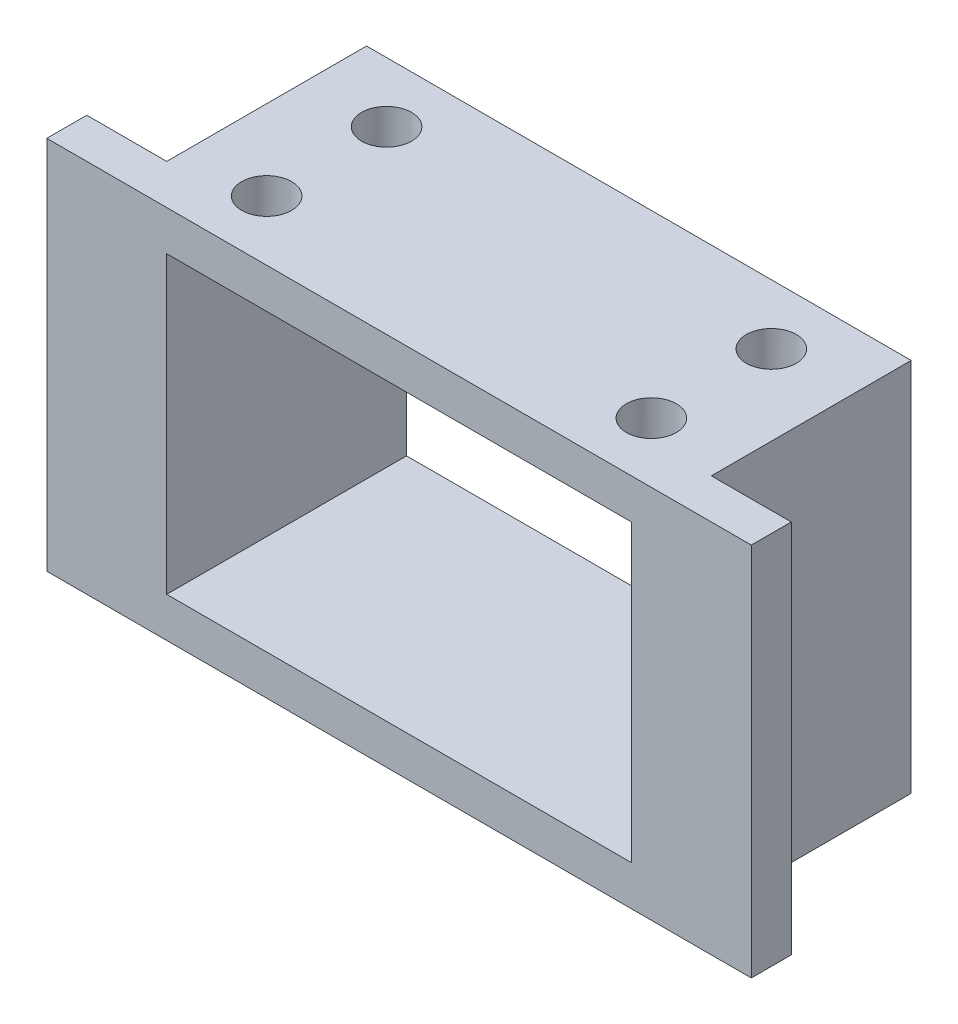
SolidWorks part; units mm, degrees
ref_plane "Front Plane" through (0, 0, 0) normal (0, 0, 1) x (1, 0, 0)
ref_plane "Top Plane" through (0, 0, 0) normal (0, 1, 0) x (1, 0, 0)
ref_plane "Right Plane" through (0, 0, 0) normal (1, 0, 0) x (0, 0, -1)
sketch "Sketch1" plane through (0, 0, 0) normal (0, 0, 1) x (1, 0, 0)
  line L0 (-2, 2) -> (25.25, 2)
  line L1 (0, 0) -> (23.25, 0)
  line L2 (0, 0) -> (0, -14.76)
  line L3 (0, -14.76) -> (23.25, -14.76)
  line L4 (23.25, 0) -> (23.25, -14.76)
  line L5 (25.25, 2) -> (25.25, -16.76)
  line L6 (-2, -16.76) -> (25.25, -16.76)
  line L7 (-2, 2) -> (-2, -16.76)
  dimension "D1" = 14.76
  dimension "D2" = 23.25
  dimension "D3" = 2
extrude "Boss-Extrude1" add sketch "Sketch1" along normal blind 18
sketch "Sketch3" plane through (0, 0, 0) normal (0, 0, -1) x (-1, 0, 0)
  line L1 (-23.25, 0) -> (0, 0)
  line L2 (-23.25, 0) -> (-23.25, -14.76)
  line L3 (-23.25, -14.76) -> (0, -14.76)
  line L4 (0, 0) -> (0, -14.76)
extrude "Boss-Extrude2" add sketch "Sketch3" against normal blind 2
sketch "Sketch7" plane through (-2, 0, 0) normal (-1, 0, 0) x (0, 0, 1)
  line L0 (18, 2) -> (0, 2) construction
  line L1 (2, -4) -> (4, -4)
  line L2 (2, -4) -> (2, -9)
  line L3 (2, -9) -> (4, -9)
  line L4 (4, -4) -> (4, -9)
  line L6 (0, 2) -> (0, -16.76) construction
  dimension "D1" = 6
  dimension "D2" = 5
  dimension "D3" = 2
  dimension "D4" = 2
extrude "Cut-Extrude1" cut sketch "Sketch7" against normal blind 2
sketch "Sketch10" plane through (0, 0, 18) normal (0, 0, 1) x (1, 0, 0)
  line L1 (-2, 2) -> (25.25, 2)
  line L2 (-2, 2) -> (-2, -16.76)
  line L3 (-2, -16.76) -> (25.25, -16.76)
  line L4 (25.25, 2) -> (25.25, -16.76)
  line L5 (0, 0) -> (23.25, 0)
  line L6 (0, 0) -> (0, -14.76)
  line L7 (0, -14.76) -> (23.25, -14.76)
  line L8 (23.25, 0) -> (23.25, -14.76)
  line L10 (-2, -0.0396) -> (-2, -13.0396)
  line L13 (-2, 2) -> (-9, 2)
  line L14 (-2, 2) -> (-2, -16.76)
  line L15 (-2, -16.76) -> (-9, -16.76)
  line L16 (-9, 2) -> (-9, -16.76)
  line L17 (25.25, 2) -> (32.25, 2)
  line L18 (25.25, 2) -> (25.25, -16.76)
  line L19 (25.25, -16.76) -> (32.25, -16.76)
  line L20 (32.25, 2) -> (32.25, -16.76)
  line M7 (-2, 2) -> (-2, -16.76)
  line M8 (-2, -16.76) -> (25.25, -16.76)
  line M9 (25.25, -16.76) -> (25.25, 2)
  line M10 (25.25, 2) -> (-2, 2)
  line M11 (23.25, -14.76) -> (0, -14.76)
  line M12 (0, -14.76) -> (0, 0)
  line M13 (0, 0) -> (23.25, 0)
  line M14 (23.25, 0) -> (23.25, -14.76)
  dimension "D1" = 7
  dimension "D2" = 7
extrude "Boss-Extrude3" add sketch "Sketch10" along normal blind 2 contours L13 L16 L15 L2 M7 | L2 M10 M7 M8 M9 M14 M11 M12 M13 | L20 L17 L19 M9 region at (11.625, 1.6692, 18) region at (-5.5, -7.38, 18) region at (28.75, -7.38, 18)
sketch "Sketch11" plane through (0, 0, 18) normal (0, 0, -1) x (-1, 0, 0)
  line L0 (2, 2) -> (9, 2) construction
  line L1 (6, 2) -> (3, 2)
  line L3 (6, -16.76) -> (3, -16.76)
  line L5 (2, -16.76) -> (9, -16.76) construction
  line L7 (2, 2) -> (2, -16.76) construction
  circle A0 centre (3.5, -8.26) radius 1.5
  dimension "D1" = 8.5
  dimension "D2" = 1.5
extrude "Cut-Extrude3" cut sketch "Sketch11" against normal blind 2 contours A0 | A0 | A0 | A0 region at (-3.5, -8.26, 18)
sketch "Sketch12" plane through (0, 0, 18) normal (0, 0, -1) x (-1, 0, 0)
  line L0 (-32.25, 2) -> (-25.25, 2) construction
  line L1 (-31, 2) -> (-28, 2)
  line L3 (-31, -16.76) -> (-28, -16.76)
  line L5 (-32.25, -16.76) -> (-25.25, -16.76) construction
  line L7 (-25.25, -16.76) -> (-25.25, 2) construction
  circle A0 centre (-26.95, -8.26) radius 1.5
  dimension "D1" = 8.5
  dimension "D2" = 1.7
extrude "Cut-Extrude4" cut sketch "Sketch12" against normal blind 2 contours A0 | A0 | A0 | A0 region at (26.95, -8.26, 18)
fillet "Fillet11" radius 1 6 edges at (0, -9, 3) (0, -4, 3) (0, -6.5, 4) (-2, -6.5, 4) (-2, -4, 3) (-2, -9, 3)
sketch "Sketch13" plane through (0, 0, 18) normal (0, 0, -1) x (-1, 0, 0)
  line L0 (-32.25, -16.76) -> (-25.25, -16.76) construction
  line L1 (-32.25, 2) -> (-29.25, 2)
  line L2 (-32.25, 2) -> (-32.25, -16.76)
  line L3 (-32.25, -16.76) -> (-29.25, -16.76)
  line L4 (-29.25, 2) -> (-29.25, -16.76)
  line L5 (2, -16.76) -> (9, -16.76) construction
  line L6 (9, 2) -> (6, 2)
  line L7 (9, 2) -> (9, -16.76)
  line L8 (9, -16.76) -> (6, -16.76)
  line L9 (6, 2) -> (6, -16.76)
  dimension "D1" = 3
  dimension "D2" = 3
extrude "Cut-Extrude5" cut sketch "Sketch13" against normal blind 10
sketch "Sketch14" plane through (0, 2, 0) normal (0, 1, 0) x (1, 0, 0)
  line L0 (25.25, -18) -> (25.25, 0) construction
  line L1 (-2, 0) -> (25.25, 0)
  line L2 (-2, 0) -> (-2, -8)
  line L3 (-2, -8) -> (25.25, -8)
  line L4 (25.25, 0) -> (25.25, -8)
  line L5 (-2, -18) -> (-6, -18) construction
  dimension "D1" = 10
extrude "Cut-Extrude6" cut sketch "Sketch14" against normal up to surface (18.76 mm away) up to face at (11.625, -16.76, 14)
sketch "Sketch16" plane through (0, 0, 20) normal (0, 0, 1) x (1, 0, 0)
  line L5 (0, -14.76) -> (0, -16.76)
  line L6 (29.25, -16.76) -> (-6, -16.76) construction
  line L7 (0, -16.76) -> (23.25, -16.76)
  line L8 (23.25, -16.76) -> (23.25, -14.76)
  line L10 (0, -14.76) -> (23.25, -14.76)
  line L14 (23.25, -14.76) -> (23.25, 0)
  line L15 (0, -14.76) -> (23.25, -14.76)
  line L16 (0, 0) -> (0, -14.76)
  line L17 (23.25, 0) -> (0, 0)
  line L18 (23.25, -14.76) -> (23.25, 0)
  line L20 (0, 0) -> (0, -14.76)
  line L21 (23.25, 0) -> (0, 0)
  line M4 (-6, -16.76) -> (29.25, -16.76)
  line M8 (23.25, -14.76) -> (0, -14.76)
  dimension "D1" = 0
extrude "Boss-Extrude5" add sketch "Sketch16" along normal blind 7.6 contours L8 L5 M4 M8 region at (11.625, -15.76, 20)
sketch "Sketch19" plane through (0, 0, 8) normal (0, 0, -1) x (-1, 0, 0)
  line L0 (-26.95, -6.76) -> (-23.25, -6.76)
  line L1 (-23.25, -14.76) -> (-23.25, 0) construction
  line L2 (-23.25, -6.76) -> (-23.25, -7.75)
  line L3 (-23.25, -7.75) -> (-25.25, -7.75)
  line L4 (-25.25, -16.76) -> (-25.25, 2) construction
  line L5 (-25.25, -7.75) -> (-25.25, -6.76)
  line L6 (-25.25, -16.76) -> (-25.25, 2) construction
  line L7 (3.5, -6.76) -> (0, -6.76)
  line L8 (0, 0) -> (0, -14.76) construction
  line L9 (0, -6.76) -> (0, -7.75)
  line L10 (0, -7.75) -> (2, -7.75)
  line L11 (2, -8.26) -> (2, -16.76) construction
  line L12 (2, -7.75) -> (2, -6.76)
  line L13 (2, 2) -> (2, -8.26) construction
  line L14 (-25.25, -6.76) -> (-23.25, -6.76)
  line L15 (-23.25, -7.75) -> (-25.25, -7.75)
  line L16 (0, -6.76) -> (2, -6.76)
  line L17 (2, -7.75) -> (0, -7.75)
  circle A0 centre (-26.95, -8.26) radius 1.5 construction
  circle A1 centre (3.5, -8.26) radius 1.5 construction
  line M1 (0, 0) -> (0, -14.76)
  line M3 (-23.25, -14.76) -> (-23.25, 0)
  line M6 (2, -16.76) -> (2, 2)
  line M8 (-25.25, 2) -> (-25.25, -16.76)
extrude "Cut-Extrude8" cut sketch "Sketch19" against normal up to surface (10 mm away) contours L10 L7 M1 M6 | L3 L0 M3 M8 region at (24.25, -7.255, 8) region at (-1, -7.255, 8) up to face at (25.45, -8.26, 18)
sketch "Sketch20" plane through (0, -16.76, 0) normal (0, -1, 0) x (1, 0, 0)
  line L0 (2, 17) -> (18.6, 17)
  line L1 (25.25, 8) -> (-2, 8) construction
  line L2 (-2, 18) -> (-2, 8) construction
  line L3 (1.3222, 20.5938) -> (20.8547, 23.0246)
  line L4 (1.5074, 19.1053) -> (21.0399, 21.536)
  line L5 (1.0027, 14.9575) -> (19.59, 12.6444)
  line L6 (0.8174, 13.469) -> (19.4048, 11.1559)
  circle A0 centre (18.6, 17) radius 4.2
  circle A1 centre (2, 17) radius 2.15
  circle A2 centre (2, 17) radius 3.65
  circle A3 centre (18.6, 17) radius 5.7
  line M9 (29.25, 20) -> (23.25, 20)
  line M10 (23.25, 20) -> (23.25, 27.6)
  line M12 (0, 27.6) -> (0, 20)
  line M13 (0, 20) -> (-6, 20)
  dimension "D1" = 8.4
  dimension "D2" = 4.3
  dimension "D3" = 16.6
  dimension "D4" = 9
  dimension "D5" = 4
  dimension "D6" = 1.5
  dimension "D7" = 1.5
extrude "Boss-Extrude6" add sketch "Sketch20" along normal blind 4 contours L4 A2 L5 A1 M12 M13 | A3 L3 A2 L4 | A3 L4 A0 L5 M10 M9 | A3 L5 A2 L6 region at (-0.2465, -16.76, 17) region at (9.5346, -16.76, 20.9168) region at (9.5346, -16.76, 13.0832) region at (15.9644, -16.76, 21.8821)
sketch "Sketch21" plane through (0, -16.76, 0) normal (0, -1, 0) x (1, 0, 0)
  circle A0 centre (18.6, 17) radius 1.25
  dimension "D1" = 2.5
extrude "Cut-Extrude9" cut sketch "Sketch21" against normal up to surface (2 mm away) up to face at (11.625, -14.76, 18.5333)
sketch "Sketch23" plane through (0, -16.76, 0) normal (0, -1, 0) x (1, 0, 0)
  line L0 (11.1, 21.1007) -> (0.4062, 19.9989)
  line L1 (0.4062, 19.9989) -> (-0.9545, 17.32)
  line L2 (-0.9545, 17.32) -> (0.3877, 14.426)
  line L3 (0.3877, 14.426) -> (11.1, 12.8678)
  line L4 (11.1, 12.8678) -> (11.1, 21.1007)
  circle A0 centre (18.6, 17) radius 1.25 construction
  dimension "D1" = 7.5
extrude "Boss-Extrude7" add sketch "Sketch23" along normal blind 1
sketch "Sketch24" plane through (0, -16.76, 0) normal (0, -1, 0) x (1, 0, 0)
  line L0 (0.8326, 20.5329) -> (21.7275, 23.1332)
  line L1 (0, 20) -> (0, 27.6)
  line L2 (0, 27.6) -> (23.25, 27.6)
  line L3 (23.25, 27.6) -> (23.25, 20)
  circle A0 centre (2, 17) radius 3.65
  circle A1 centre (18.6, 17) radius 5.7
  arc M2 (17.8961, 22.6564) -> (23.25, 20.2966) centre (18.6, 17) cw
  line M3 (23.25, 20.2966) -> (23.25, 27.6)
  line M4 (23.25, 27.6) -> (0, 27.6)
  line M5 (0, 27.6) -> (0, 20.0533)
  arc M6 (0, 20.0533) -> (1.5492, 20.6221) centre (2, 17) cw
  line M7 (1.5492, 20.6221) -> (17.8961, 22.6564)
  dimension "D1" = 7.3
  dimension "D2" = 11.4
extrude "Cut-Extrude11" cut sketch "Sketch24" against normal blind 12 contours M7 M2 M3 M4 M5 M6 region at (11.0332, -16.76, 24.5869)
sketch "Sketch26" plane through (0, -20.76, 0) normal (0, -1, 0) x (1, 0, 0)
  line L1 (-3.2997, 26.072) -> (24.7866, 26.072)
  line L2 (-3.2997, 26.072) -> (-3.2997, 10.6963)
  line L3 (-3.2997, 10.6963) -> (24.7866, 10.6963)
  line L4 (24.7866, 26.072) -> (24.7866, 10.6963)
extrude "Cut-Extrude13" cut sketch "Sketch26" against normal up to surface (4 mm away) up to face at (11.355, -16.76, 15.8677)
sketch "Sketch27" plane through (0, -16.76, 0) normal (0, -1, 0) x (-1, 0, 0)
  line L1 (0, -20) -> (-24.0759, -20)
  line L2 (0, -20) -> (0, -23.8722)
  line L3 (0, -23.8722) -> (-24.0759, -23.8722)
  line L4 (-24.0759, -20) -> (-24.0759, -23.8722)
extrude "Cut-Extrude14" cut sketch "Sketch27" against normal blind 12
sketch "Sketch28" plane through (0, -16.76, 0) normal (0, -1, 0) x (1, 0, 0)
  line L1 (16.2991, 18.936) -> (21.7388, 18.936)
  line L2 (16.2991, 18.936) -> (16.2991, 13.8993)
  line L3 (16.2991, 13.8993) -> (21.7388, 13.8993)
  line L4 (21.7388, 18.936) -> (21.7388, 13.8993)
extrude "Boss-Extrude8" add sketch "Sketch28" against normal up to surface (2 mm away) up to face at (11.625, -14.76, 14)
sketch "Sketch29" plane through (0, 2, 0) normal (0, 1, 0) x (1, 0, 0)
  line L2 (-2, -8) -> (25.25, -8) construction
  line L3 (29.25, -20) -> (-6, -20) construction
  line L4 (-2, -18) -> (-2, -8) construction
  line L5 (25.25, -18) -> (25.25, -8) construction
  circle A0 centre (2, -11) radius 1.25
  circle A1 centre (21.25, -11) radius 1.25
  circle A2 centre (2, -17) radius 1.25
  circle A3 centre (21.25, -17) radius 1.25
  dimension "D1" = 2.5
  dimension "D2" = 2.5
  dimension "D3" = 2.5
  dimension "D4" = 2.5
  dimension "D7" = 3
  dimension "D8" = 3
  dimension "D9" = 4
  dimension "D10" = 4
  dimension "D11" = 4
  dimension "D12" = 4
  dimension "D5" = 3
  dimension "D6" = 3
extrude "Cut-Extrude15" cut sketch "Sketch29" against normal up to surface (2 mm away) up to face at (11.625, 0, 14)
sketch "Sketch30" plane through (0, 0, 18) normal (0, 0, -1) x (-1, 0, 0)
  line L1 (-25.25, -6.76) -> (-23.25, -6.76)
  line L2 (-25.25, -6.76) -> (-25.25, -7.75)
  line L3 (-25.25, -7.75) -> (-23.25, -7.75)
  line L4 (-23.25, -6.76) -> (-23.25, -7.75)
  line L5 (0, -6.76) -> (2, -6.76)
  line L6 (0, -6.76) -> (0, -7.75)
  line L7 (0, -7.75) -> (2, -7.75)
  line L8 (2, -6.76) -> (2, -7.75)
extrude "Boss-Extrude9" add sketch "Sketch30" along normal blind 10
sketch "Sketch32" plane through (0, 0, 20) normal (0, 0, 1) x (1, 0, 0)
  line L1 (-5.4728, -3.4844) -> (-1.6186, -3.4844)
  line L2 (-5.4728, -3.4844) -> (-5.4728, -8.9786)
  line L3 (-5.4728, -8.9786) -> (-1.6186, -8.9786)
  line L4 (-1.6186, -3.4844) -> (-1.6186, -8.9786)
  line L5 (24.3356, -3.1154) -> (28.8458, -3.1154)
  line L6 (24.3356, -3.1154) -> (24.3356, -8.9786)
  line L7 (24.3356, -8.9786) -> (28.8458, -8.9786)
  line L8 (28.8458, -3.1154) -> (28.8458, -8.9786)
extrude "Boss-Extrude11" add sketch "Sketch32" against normal blind 2
sketch "Sketch33" plane through (0, 0, 20) normal (0, 0, 1) x (1, 0, 0)
  line L1 (-5.5548, -7.7695) -> (-2.8487, -7.7695)
  line L2 (-5.5548, -7.7695) -> (-5.5548, -9.8606)
  line L3 (-5.5548, -9.8606) -> (-2.8487, -9.8606)
  line L4 (-2.8487, -7.7695) -> (-2.8487, -9.8606)
  line L5 (-1.2086, -10.7217) -> (-5.5548, -10.7217)
  line L6 (-1.2086, -10.7217) -> (-1.2086, -6.5805)
  line L7 (-1.2086, -6.5805) -> (-5.5548, -6.5805)
  line L8 (-5.5548, -10.7217) -> (-5.5548, -6.5805)
  line L9 (28.8458, -11.4187) -> (23.5975, -11.4187)
  line L10 (28.8458, -11.4187) -> (28.8458, -7.1545)
  line L11 (28.8458, -7.1545) -> (23.5975, -7.1545)
  line L12 (23.5975, -11.4187) -> (23.5975, -7.1545)
  arc M5 (28.2667, -8.9786) -> (25.6333, -8.9786) centre (26.95, -8.26) cw
  line M6 (25.6333, -8.9786) -> (28.2667, -8.9786)
  arc M7 (-2.1833, -8.9786) -> (-4.8167, -8.9786) centre (-3.5, -8.26) cw
  line M8 (-4.8167, -8.9786) -> (-2.1833, -8.9786)
extrude "Boss-Extrude13" add sketch "Sketch33" against normal blind 2 contours L4 M8 M7 | L4 M8 M7 | M5 M6 region at (-2.6042, -9.2114, 20) region at (-3.6887, -9.3179, 20) region at (26.95, -9.2994, 20)
